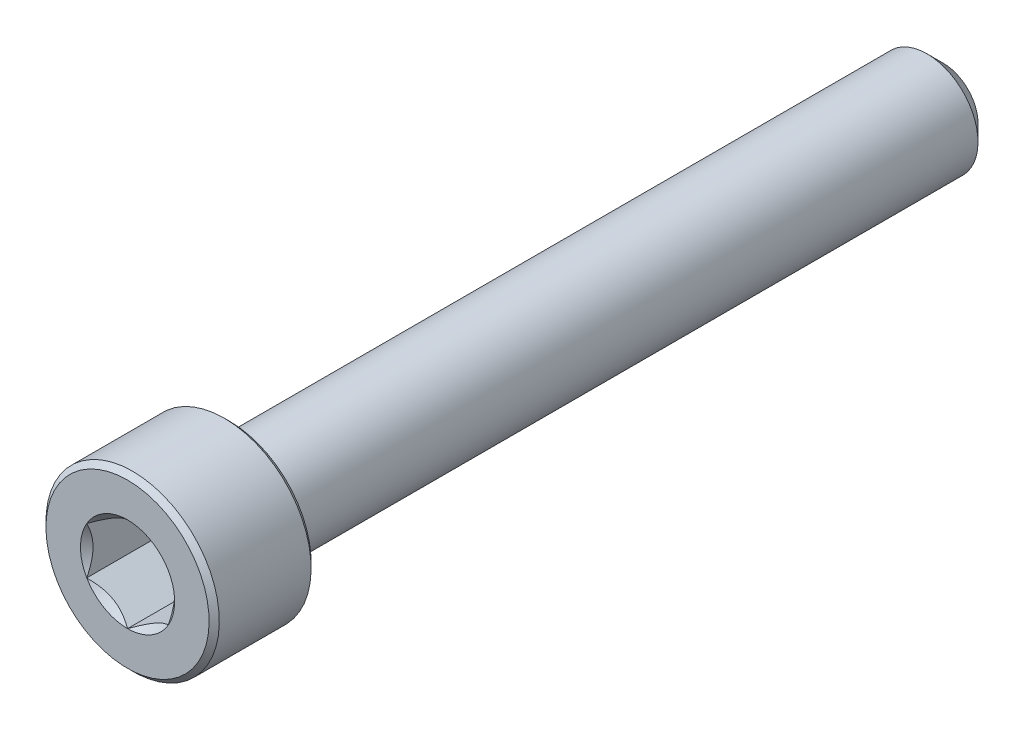
SolidWorks part; units mm, degrees
ref_plane "Front Plane" through (0, 0, 0) normal (0, 0, 1) x (1, 0, 0)
ref_plane "Top Plane" through (0, 0, 0) normal (0, 1, 0) x (1, 0, 0)
ref_plane "Right Plane" through (0, 0, 0) normal (1, 0, 0) x (0, 0, -1)
sketch "Sketch1" plane through (0, 0, 0) normal (1, 0, 0) x (0, 0, -1)
  line L0 (-20, 0) -> (20, 0) construction
  line L1 (20, 0) -> (20, 1.7) construction
  line L2 (20, 1.7) -> (19.2, 2.5) construction
  line L3 (19.2, 2.5) -> (19.4, 2.5) construction
  line L4 (19.4, 2.5) -> (-15, 2.5) construction
  line L5 (-15, 2.5) -> (-15, 4.25) construction
  line L6 (-15, 4.25) -> (-20, 4.25) construction
  line L7 (-20, 4.25) -> (-20, 0) construction
  line L8 (20, 1.7) -> (20, 2.5) construction
  line L9 (19.95, 2.5866) -> (20.35, 1.8938) construction
  line L10 (20.35, 1.8938) -> (20.75, 2.5866) construction
  line L11 (20.75, 2.5866) -> (19.95, 2.5866) construction
  line L12 (20.35, 2.5866) -> (20.35, 2.5) construction
  line L13 (20.35, 1.8938) -> (20.35, 1.9804) construction
  line L14 (20.3, 1.9804) -> (20.4, 1.9804) construction
  line L15 (20, 2.5) -> (20.7, 2.5) construction
  line L16 (19.975, 2.5433) -> (20.725, 2.5433) construction
  line L17 (20, 0) -> (20, -2.5) construction
  line L18 (-15.25, 4.25) -> (-15, 4) construction
  line L19 (-19.75, 4.25) -> (-20, 4) construction
  line L20 (-15, 2.5) -> (-15, 0) construction
  line L21 (-15, 1.25) -> (-3.3333, 1.25) construction
  line L22 (-3.3333, 1.25) -> (8.3333, 1.25) construction
  line L23 (8.3333, 1.25) -> (20, 1.25) construction
  line L24 (-3.3333, 1.25) -> (-3.3333, 2.5) construction
  line L25 (-3.3333, 2.5) -> (-3.3333, 4.25) construction
  line L26 (8.3333, 1.25) -> (8.3333, 4.25) construction
  point P0 (-20, 2)
  point P3 (18, 2.5)
  point P4 (0, 0)
  point P18 (8.3333, 2.5)
  point P22 (20.35, 1.9804)
  point P24 (19.4, 2.5)
  point P25 (20.35, 2.5)
  point P28 (20.35, 2.5433)
  point P29 (18, -2.5)
  point P30 (-3.3333, 2.5)
  point P31 (-17.5, 4.25)
  point P37 (-15.875, 4.25)
  point P38 (-19.625, 4.25)
  point P45 (-3.3333, 1.25)
  point P46 (8.3333, 1.25)
  dimension "D1" = 45
  dimension "D2" = 0.1
  dimension "D3" = 0.8
  dimension "D7" = 0.25
  dimension "D8" = 0.25
  dimension "D9" = 0.25
  dimension "D10" = 0.125
  dimension "D11" = 0.625
  dimension "Drive Size" = 4
  dimension "Head Diameter" = 8.5
  dimension "Head Height" = 5
  dimension "Thread Pitch" = 0.8
  dimension "Thread Major Diameter" = 5
  dimension "Length" = 35
  dimension "D12" = 0.6
  dimension "D4" = 2
sketch "Sketch2" plane through (0, 0, 0) normal (1, 0, 0) x (0, 0, -1)
  line L0 (-20, 0) -> (-20, 4)
  line L1 (-19.75, 4.25) -> (-15.25, 4.25)
  line L2 (-15, 4) -> (-15, 2.5)
  line L3 (-15, 2.5) -> (19.2, 2.5)
  line L4 (19.2, 2.5) -> (20, 1.7)
  line L5 (20, 1.7) -> (20, 0)
  line L6 (-15.25, 4.25) -> (-15, 4) construction
  line L7 (20, 0) -> (-20, 0)
  line L8 (-19.75, 4.25) -> (-20, 4) construction
  line L9 (-15.25, 4.25) -> (-15, 4)
  line L10 (-19.75, 4.25) -> (-20, 4)
revolve "Revolve1" add sketch "Sketch2" angle 360 about L7
sketch "Sketch3" plane through (0, 0, 20) normal (0, 0, 1) x (1, 0, 0)
  line L1 (2, -1.1547) -> (2, 1.1547)
  line L2 (2, 1.1547) -> (0, 2.3094)
  line L3 (0, 2.3094) -> (-2, 1.1547)
  line L4 (-2, 1.1547) -> (-2, -1.1547)
  line L5 (-2, -1.1547) -> (0, -2.3094)
  line L6 (0, -2.3094) -> (2, -1.1547)
  circle A0 centre (0, 0) radius 2 construction
extrude "Cut-Extrude1" cut sketch "Sketch3" against normal offset from surface (4 mm away) 1 up to face at (0, 4, 15)
sketch "Sketch4" plane through (0, 0, 20) normal (0, 0, 1) x (1, 0, 0)
  circle A0 centre (0, 0) radius 2.3094
extrude "Cut-Extrude2" cut sketch "Sketch4" against normal up to vertex (2.5 mm away) draft 45 up to point (0, 4.25, 17.5)
ref_plane "Plane1" [suppressed] through (0, 0, -19.4) normal (0, 0, 1) x (1, 0, 0)
split "Split1" [suppressed] bodies to split 106
sketch "Sketch6" [suppressed] plane through (0, 0, -20) normal (0, 0, -1) x (-1, 0, 0)
  circle A0 centre (0, 0) radius 2.5
curve "Helix/Spiral1" [suppressed] pitch 0.8 height 35.92 turns 44.9
sketch "Sketch7" [suppressed] plane through (0, 0, 0) normal (1, 0, 0) x (0, 0, -1)
  line L0 (19.975, 2.5433) -> (20.725, 2.5433)
  line L1 (20.725, 2.5433) -> (20.4, 1.9804)
  line L2 (20.4, 1.9804) -> (20.3, 1.9804)
  line L3 (20.3, 1.9804) -> (19.975, 2.5433)
sweep "Cut-Sweep1" [suppressed] cut profiles "Sketch7" path "Helix/Spiral1"
sketch "Sketch8" [suppressed] plane through (0, 0, 15) normal (0, 0, -1) x (-1, 0, 0)
  circle A0 centre (0, 0) radius 2.5
extrude "Boss-Extrude1" [suppressed] add sketch "Sketch8" along normal through all draft 45
equation "\"D2@Sketch1\" = \"Thread Pitch@Sketch1\" / 8"
equation "\"D3@Sketch1\"= \"Thread Pitch@Sketch1\""
equation "\"D4@Helix/Spiral1\" = \"Thread Pitch@Sketch1\""
equation "\"D7@Sketch1\" = \"Head Height@Sketch1\" * .05"
equation "\"D8@Sketch1\"=\"D7@Sketch1\""
equation "\"D9@Sketch1\"=\"D7@Sketch1\""
equation "\"D10@Sketch1\"=\"D7@Sketch1\"/2"
equation "\"D11@Sketch1\"=\"D10@Sketch1\"*5"
equation "\"D4@Sketch1\"=\"Thread Pitch@Sketch1\"*2.5"
equation "\"D12@Sketch1\"=\"Thread Pitch@Sketch1\"*.75"
